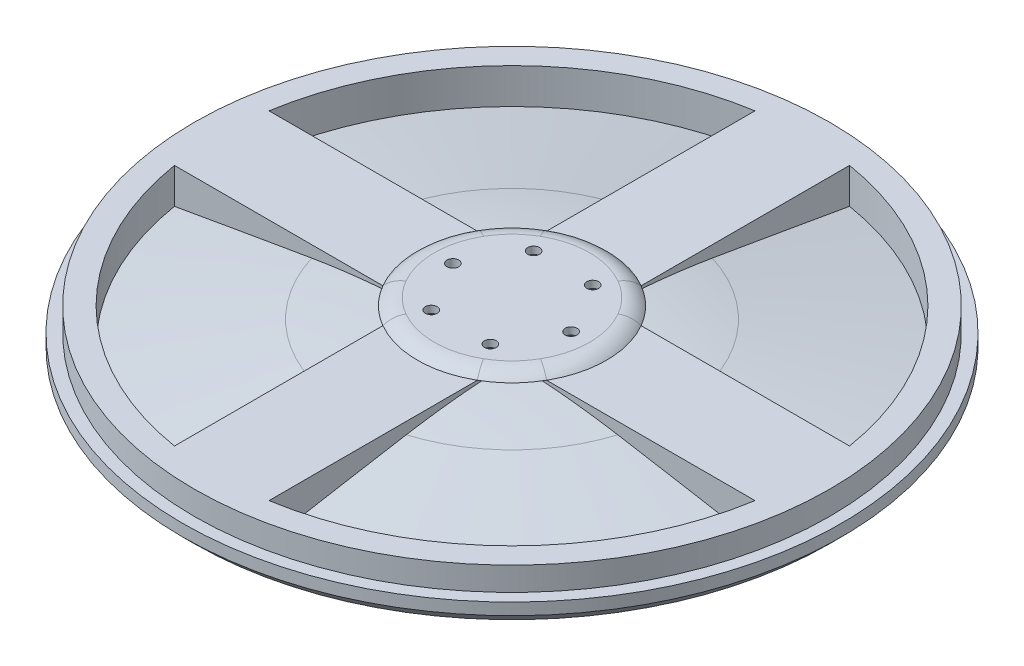
SolidWorks part; units mm, degrees
ref_plane "Front" through (0, 0, 0) normal (0, 0, 1) x (1, 0, 0)
ref_plane "Top" through (0, 0, 0) normal (0, 1, 0) x (1, 0, 0)
ref_plane "Right" through (0, 0, 0) normal (1, 0, 0) x (0, 0, -1)
sketch "草图1" plane through (0, 0, 0) normal (0, 1, 0) x (1, 0, 0)
  circle A0 centre (0, 0) radius 13.945
  dimension "D1" = 27.89
extrude "凸台-拉伸1" add sketch "草图1" along normal blind 0.5
sketch "草图7" plane through (0, 0.5, 0) normal (0, 1, 0) x (1, 0, 0)
  circle A0 centre (0, 0) radius 1
  dimension "D1" = 2
extrude "切除-拉伸6" cut sketch "草图7" against normal blind 0.3
sketch "草图8" plane through (0, 0.5, 0) normal (0, 1, 0) x (1, 0, 0)
  circle A0 centre (0, 0) radius 13.945
  circle A1 centre (0, 0) radius 12.445
  circle A2 centre (0, 0) radius 13.945 construction
  dimension "D1" = 1.5
extrude "凸台-拉伸3" add sketch "草图8" along normal blind 0.5
sketch "草图9" plane through (0, 1, 0) normal (0, 1, 0) x (1, 0, 0)
  circle A0 centre (0, 0) radius 12.445
  circle A1 centre (0, 0) radius 13.445
  dimension "D1" = 1
extrude "凸台-拉伸4" add sketch "草图9" along normal blind 1
chamfer "倒角1" distance 0.5 angle 45 1 edges at (0, 0, 13.945)
sketch "草图10" plane through (0, 0.5, 0) normal (0, 1, 0) x (1, 0, 0)
  circle A0 centre (0, 0) radius 4
  dimension "D1" = 8
extrude "凸台-拉伸5" add sketch "草图10" along normal blind 1.5
loft "放样1" add section edge at (0, 0.5, 12.445) section edge at (0, 2, 4) connector at (7.3023, 0.5, 10.0774) connector at (1.7862, 2, 3.579)
fillet "圆角5" radius 32 1 edges at (0, 2, 4)
sketch "草图13" plane through (0, 0, 0) normal (0, -1, 0) x (1, 0, 0)
  line L0 (0, 17.9095) -> (0, -12.8328) construction
  line L1 (2.4927, 2) -> (2.4927, -2)
  line L2 (-2, 2.4927) -> (2, 2.4927)
  line L3 (-2, 2.4927) -> (-2, 13.0101)
  line L4 (-2, 13.0101) -> (2, 13.0101)
  line L5 (2, 2.4927) -> (2, 13.0101)
  line L6 (-2, 2.4927) -> (2, 13.0101) construction
  line L7 (-2, 13.0101) -> (2, 2.4927) construction
  line L8 (2.4927, 2) -> (13.0101, 2)
  line L9 (13.0101, 2) -> (13.0101, -2)
  line L10 (2.4927, -2) -> (13.0101, -2)
  line L11 (2.4927, 2) -> (13.0101, -2) construction
  line L12 (13.0101, 2) -> (2.4927, -2) construction
  line L13 (2, -2.4927) -> (-2, -2.4927)
  line L14 (2, -2.4927) -> (2, -13.0101)
  line L15 (2, -13.0101) -> (-2, -13.0101)
  line L16 (-2, -2.4927) -> (-2, -13.0101)
  line L17 (2, -2.4927) -> (-2, -13.0101) construction
  line L18 (2, -13.0101) -> (-2, -2.4927) construction
  line L19 (-2.4927, -2) -> (-2.4927, 2)
  line L20 (-2.4927, -2) -> (-13.0101, -2)
  line L21 (-13.0101, -2) -> (-13.0101, 2)
  line L22 (-2.4927, 2) -> (-13.0101, 2)
  line L23 (-2.4927, -2) -> (-13.0101, 2) construction
  line L24 (-13.0101, -2) -> (-2.4927, 2) construction
  point P3 (0, 7.7514)
  point P11 (7.7514, 0)
  point P16 (0, -7.7514)
  point P21 (-7.7514, 0)
  point P26 (0, 0)
  dimension "D1" = 4
  dimension "D2" = 4
extrude "凸台-拉伸8" add sketch "草图13" against normal blind 2
sketch "草图15" plane through (0, 2, 0) normal (0, 1, 0) x (1, 0, 0)
  circle A0 centre (0, 0) radius 4
  dimension "D1" = 8
extrude "凸台-拉伸9" add sketch "草图15" along normal blind 0.3
fillet "圆角6" radius 1 1 edges at (0, 2.3, 4)
sketch "草图16" plane through (0, 2.3, 0) normal (0, 1, 0) x (1, 0, 0)
  line L0 (-15.7864, 0) -> (19.7036, 0) construction
  circle A0 centre (2.5, 0) radius 0.25
  dimension "D1" = 0.5
  dimension "D2" = 2.5
extrude "切除-拉伸7" cut sketch "草图16" against normal blind 1
pattern_circular "阵列(圆周)1" count 6 every 60 of "切除-拉伸7"
